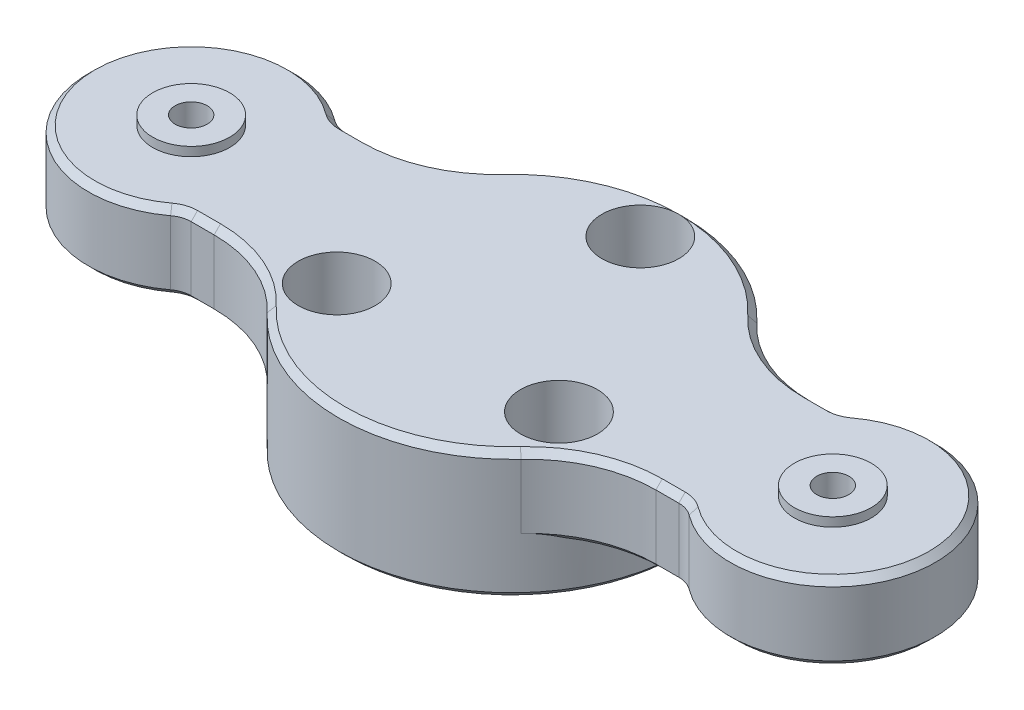
SolidWorks part; units mm, degrees
material "6061 合金"
ref_plane "Front Plane" through (0, 0, 0) normal (0, 0, 1) x (1, 0, 0)
ref_plane "Top Plane" through (0, 0, 0) normal (0, 1, 0) x (1, 0, 0)
ref_plane "Right Plane" through (0, 0, 0) normal (1, 0, 0) x (0, 0, -1)
other "Configuration Table"
sketch "草图1" plane through (0, 0, 0) normal (0, 1, 0) x (1, 0, 0)
  line L1 (0, 10) -> (-8.6603, -5) construction
  line L2 (-8.6603, -5) -> (8.6603, -5) construction
  line L3 (8.6603, -5) -> (0, 10) construction
  circle A0 centre (0, 0) radius 13.5
  circle A1 centre (0, 0) radius 10 construction
  circle A2 centre (0, 10) radius 1.6
  circle A3 centre (8.6603, -5) radius 1.6
  circle A4 centre (-8.6603, -5) radius 1.6
  point P15 (0, 0)
  dimension "D1" = 27
  dimension "D2" = 20
  dimension "D3" = 3.2
  dimension "D4" = 3
extrude "凸台-拉伸1" add sketch "草图1" along normal blind 10
sketch "草图2" plane through (0, 10, 0) normal (0, 1, 0) x (1, 0, 0)
  line L0 (-25, 0) -> (25, 0) construction
  line L1 (0, 13.5) -> (0, -13.5) construction
  line L2 (-19.7085, 6) -> (-12.0934, 6)
  line L3 (-19.7085, -6) -> (-12.0934, -6)
  line L4 (19.7085, -6) -> (12.0934, -6)
  line L5 (19.7085, 6) -> (12.0934, 6)
  arc A0 (-19.7085, 6) -> (-19.7085, -6) centre (-25, 0) ccw
  circle A1 centre (-25, 0) radius 1
  circle A2 centre (0, 0) radius 13.5 construction
  arc A3 (-12.0934, 6) -> (-12.0934, -6) centre (0, 0) ccw
  arc A4 (12.0934, -6) -> (0, 13.5) centre (0, 0) ccw
  arc A5 (12.0934, 6) -> (12.0934, -6) centre (0, 0) cw
  circle A6 centre (25, 0) radius 1
  arc A7 (19.7085, 6) -> (19.7085, -6) centre (25, 0) cw
  point P3 (0, 0)
  circle M7 centre (0, 0) radius 13.5
  dimension "D2" = 16
  dimension "D3" = 2
  dimension "D1" = 25
  dimension "D4" = 6
extrude "凸台-拉伸2" add sketch "草图2" against normal blind 6 contours L2 A0 L3 A1 M7 | A7 L5 L4 A6 M7
sketch "草图3" plane through (0, 10, 0) normal (0, 1, 0) x (1, 0, 0)
  circle A0 centre (0, 10) radius 3
  circle A1 centre (8.6603, -5) radius 3
  circle A2 centre (-8.6603, -5) radius 3
  dimension "D1" = 6
  dimension "D2" = 6
  dimension "D3" = 6
extrude "切除-拉伸1" cut sketch "草图3" against normal offset from surface (5 mm away) 5 up to face at (0, 0, 13.5)
sketch "草图4" plane through (0, 10, 0) normal (0, 1, 0) x (1, 0, 0)
  circle A0 centre (25, 0) radius 1 construction
  circle A1 centre (-25, 0) radius 1 construction
  circle A2 centre (25, 0) radius 1
  circle A3 centre (-25, 0) radius 1
  circle A4 centre (-25, 0) radius 3
  circle A5 centre (25, 0) radius 3
  dimension "D1" = 6
  dimension "D2" = 6
extrude "凸台-拉伸3" add sketch "草图4" along normal blind 0.7
fillet "圆角1" radius 10 4 edges at (12.0934, 7, 6) (12.0934, 7, -6) (-12.0934, 7, -6) (-12.0934, 7, 6)
fillet "圆角2" radius 2 4 edges at (19.7085, 7, -6) (19.7085, 7, 6) (-19.7085, 7, -6) (-19.7085, 7, 6)
hole_wizard "M3 螺纹孔1" positions "草图5" profile "草图6" tap size "M3" standard "GB" end condition through all
sketch "草图5" plane through (0, 10.7, 0) normal (0, 1, 0) x (1, 0, 0)
  point P0 (-25, 0)
  point P3 (25, 0)
sketch "草图6" plane through (-25, 10.7, 0) normal (1, 0, 0) x (0, 0, 1)
  line L0 (0, 0) -> (0, 10.7)
  line L1 (0, 10.7) -> (1.25, 10.7)
  line L2 (1.25, 10.7) -> (1.25, 0)
  line L5 (1.25, 0) -> (0, 0)
  line L11 (0, -6.35) -> (0, 107.95) construction
  dimension "通孔螺纹孔钻头直径" = 2.5
  dimension "通孔螺纹孔钻头深度" = 10.7
sketch "草图7" plane through (0, 0, 0) normal (0, -1, 0) x (1, 0, 0)
  line L0 (0, 10) -> (0, 0) construction
  line L1 (0, 0) -> (-8.6603, 5) construction
  line L2 (0, 0) -> (-8.6603, -5) construction
  circle A0 centre (0, 0) radius 10 construction
  circle A1 centre (0, 10) radius 1
  circle A2 centre (8.6603, -5) radius 1
  circle A3 centre (-8.6603, -5) radius 1
  point P3 (0, 10)
  point P10 (8.6603, -5)
  point P12 (-8.6603, -5)
  dimension "D1" = 20
  dimension "D2" = 2
  dimension "D3" = 60
  dimension "D5" = 60
  dimension "D4" = 3
hole_wizard "Ø2.0mm 暗销孔2" positions "草图7" profile "草图11" hole size "Ø2.0" standard "GB"
sketch "草图11" plane through (-8.6603, 0, -5) normal (1, 0, 0) x (0, 0, -1)
  line L0 (0, 0) -> (0, 6.6009)
  line L1 (0, 6.6009) -> (1, 6)
  line L2 (1, 6) -> (1, 0)
  line L5 (1, 0) -> (0, 0)
  line L10 (0, 6.6009) -> (-1, 6) construction
  line L11 (0, -6.35) -> (0, 107.95) construction
  dimension "孔直径" = 2
  dimension "孔深度" = 6
  dimension "导头角度" = 118
chamfer "倒角1" distance 0.5 angle 45 31 edges at (0, 0, 13.5) (33, 4, 0) (33, 10, 0) (19.6325, 10, -6.1026) (19.6325, 10, 6.1026) (18.106, 10, -6) (18.106, 4, -6) (18.106, 4, 6) (18.106, 10, 6) (13.2172, 10, -6.8325) (13.2172, 10, 6.8325) (0, 10, -13.5) (0, 10, 13.5) (-13.2172, 10, -6.8325) (-13.2172, 10, 6.8325) (-18.106, 4, -6) (-18.106, 10, -6) (-18.106, 10, 6) (-18.106, 4, 6) (-19.6325, 10, -6.1026) (-19.6325, 10, 6.1026) (-33, 10, 0) (-33, 4, 0) (-13.2172, 4, 6.8325) (-19.6325, 4, 6.1026) (-19.6325, 4, -6.1026) (-13.2172, 4, -6.8325) (13.2172, 4, 6.8325) (19.6325, 4, 6.1026) (19.6325, 4, -6.1026) (13.2172, 4, -6.8325)
chamfer "倒角2" distance 0.5 angle 60 3 edges at (0, 0, 9) (8.6603, 0, -6) (-8.6603, 0, -6) first distance on face at (0, 0, 13)
